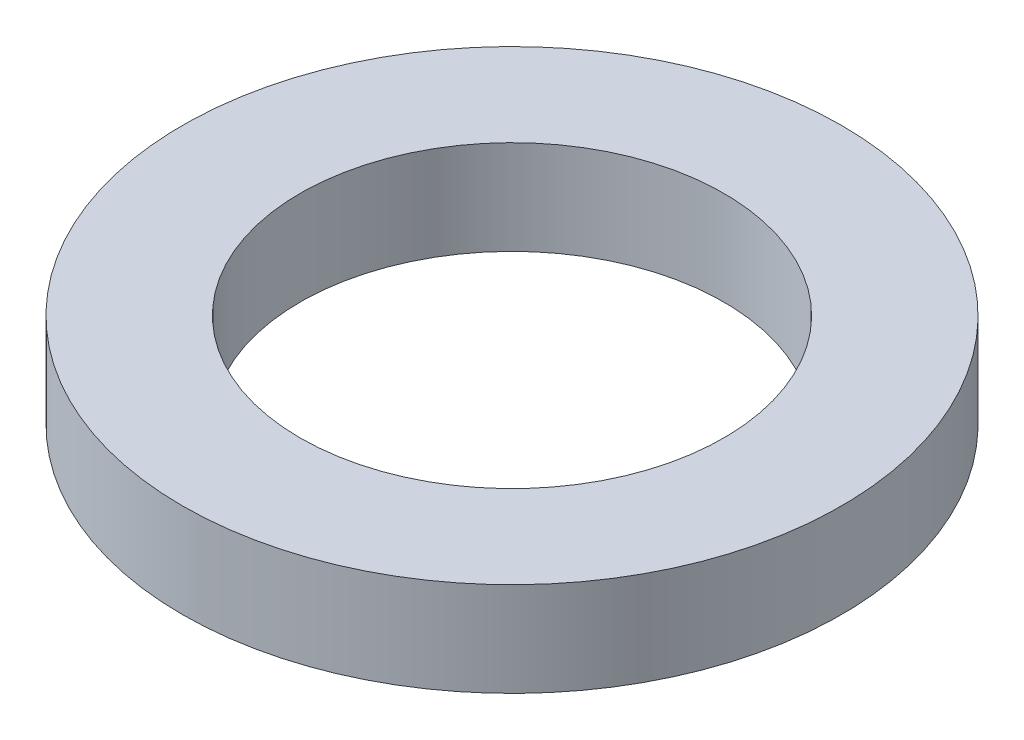
SolidWorks part; units mm, degrees
ref_plane "Front Plane" through (0, 0, 0) normal (0, 0, 1) x (1, 0, 0)
ref_plane "Top Plane" through (0, 0, 0) normal (0, 1, 0) x (1, 0, 0)
ref_plane "Right Plane" through (0, 0, 0) normal (1, 0, 0) x (0, 0, -1)
sketch "Sketch1" plane through (0, 0, 0) normal (0, 1, 0) x (1, 0, 0)
  circle A0 centre (0, 0) radius 35
  dimension "FLANGE_OD" = 70
extrude "Boss-Extrude1" add sketch "Sketch1" along normal blind 10
sketch "Sketch2" plane through (0, 0, 0) normal (0, 1, 0) x (1, 0, 0)
  circle A0 centre (0, 0) radius 22.5
  dimension "BORE_D" = 45
extrude "Cut-Extrude1" cut sketch "Sketch2" along normal through all
sketch "Sketch3" plane through (0, 10, 0) normal (0, 1, 0) x (1, 0, 0)
  circle A0 centre (0, 0) radius 12.9048 construction
  circle A1 centre (-12.9048, 0) radius 1.9943
  dimension "BOLT_D" = 3.9885
  dimension "BOLT_PCD" = 25.8097
extrude "Cut-Extrude2" cut sketch "Sketch3" against normal blind 8.5886 rebuild error yes
pattern_circular "CirPattern1" count 6 over 360 rebuild error yes
